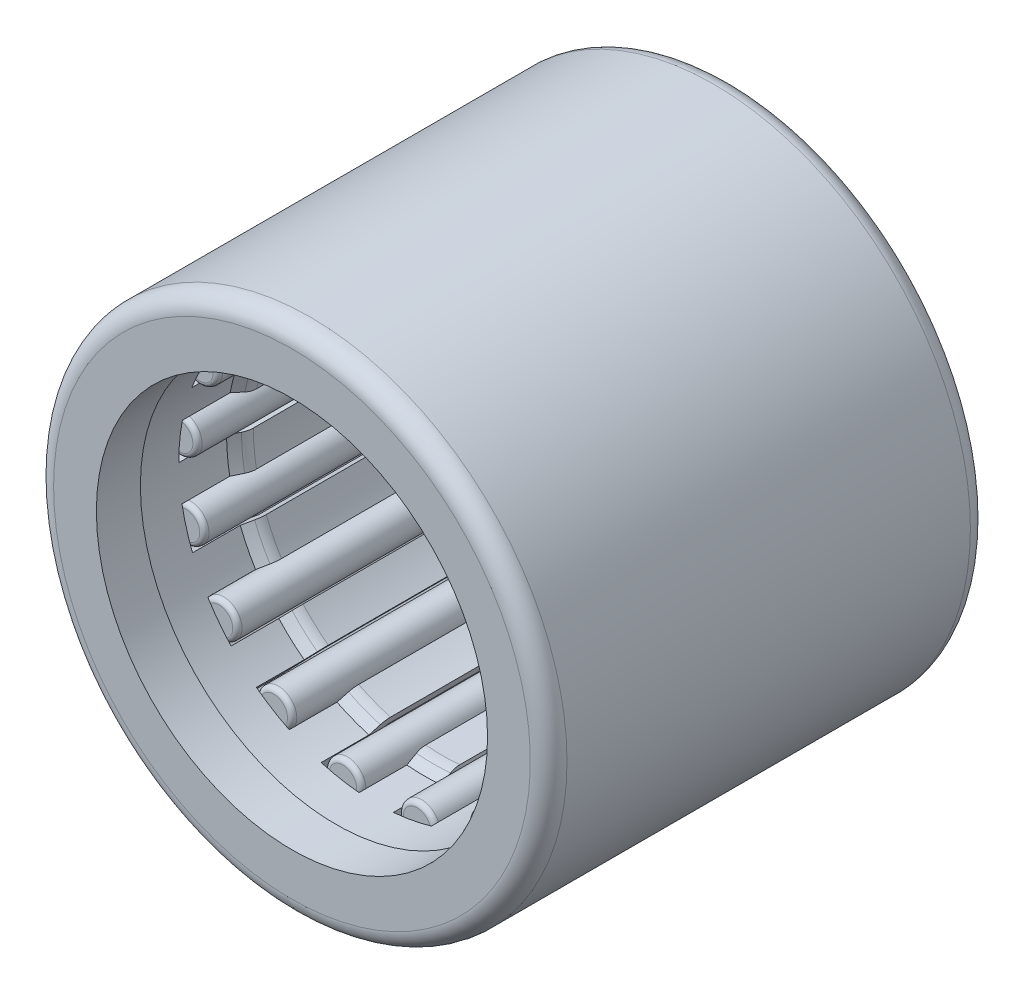
SolidWorks part; units mm, degrees
ref_plane "Front Plane" through (0, 0, 0) normal (0, 0, 1) x (1, 0, 0)
ref_plane "Top Plane" through (0, 0, 0) normal (0, 1, 0) x (1, 0, 0)
ref_plane "Right Plane" through (0, 0, 0) normal (1, 0, 0) x (0, 0, -1)
sketch "Sketch1" plane through (0, 0, 0) normal (0, 0, 1) x (1, 0, 0)
  circle A0 centre (0, 0) radius 5
  circle A1 centre (0, 0) radius 7
  dimension "OD" = 14
  dimension "ID" = 10
sketch "Sketch2" plane through (0, 0, 0) normal (1, 0, 0) x (0, 0, -1)
  line L0 (-6, 0) -> (6, 0) construction
  line L2 (-6, -5) -> (-6, 5) construction
  line L3 (6, 7) -> (-6, 7) construction
  line L11 (0, 0) -> (0, 7) construction
  line L16 (6, -7) -> (6, 7) construction
  line L17 (-6, 5) -> (6, 5) construction
  line L18 (-6, -5) -> (6, -5) construction
  point P4 (0, 0)
  point P8 (0, 7)
  point P10 (-6, 0)
  dimension "For Shaft Diameter" = 10
  dimension "Width" = 12
  dimension "For Housing ID" = 14
sketch "Sketch3" plane through (0, 0, 0) normal (1, 0, 0) x (0, 0, -1)
  line L0 (-6, -5) -> (-6, 5) construction
  line L2 (0, 7) -> (0, 6.3333) construction
  line L3 (0, 6.3333) -> (0, 5.6667) construction
  line L4 (0, 5.6667) -> (0, 5) construction
  line L16 (4.8, 6.3333) -> (4.8, 5.3333)
  line L17 (4.8, 5.3333) -> (6, 5.3333)
  line L18 (6, 5.3333) -> (6, 7)
  line L19 (6, 7) -> (-6, 7)
  line L20 (-6, 7) -> (-6, 5.3333)
  line L21 (-6, 5.3333) -> (-4.8, 5.3333)
  line L22 (-4.8, 5.3333) -> (-4.8, 6.3333)
  line L23 (-4.8, 6.3333) -> (4.8, 6.3333)
  point P17 (0, 5.3333)
  dimension "D1" = 9.6
revolve "Revolve1" add sketch "Sketch3" angle 360 about L0
fillet "Fillet1" radius 0.5 2 edges at (7, 0, -6) (7, 0, 6)
sketch "Sketch4" plane through (0, 0, 0) normal (1, 0, 0) x (0, 0, -1)
  line L0 (0, 6) -> (0, 5.5) construction
  line L2 (-6, 5.3333) -> (-4.8, 5.3333) construction
  line L3 (-3.6, 5) -> (3.6, 5)
  line L4 (-3.6, 5) -> (-3.6, 5.5)
  line L5 (-3.6, 5.5) -> (3.6, 5.5)
  line L6 (3.6, 5) -> (3.6, 5.5)
  line L7 (0, 6.3333) -> (0, 5.6667) construction
  line L8 (-3.6, 5.25) -> (3.6, 5.25) construction
  line L9 (-4.8, 5.3333) -> (-3.6, 5.3333) construction
  point P15 (3.7016, 5.3333)
  point P16 (-3.7016, 5.3333)
  dimension "D1" = 0.1016
revolve "Revolve2" add sketch "Sketch4" angle 360 about L5
fillet "Fillet2" radius 0.127 2 edges at (0.5, 5.5, 3.6) (0.5, 5.5, -3.6)
sketch "Sketch5" plane through (0, 0, 0) normal (0, 0, 1) x (1, 0, 0)
  line L0 (0, 0) -> (0.5, 5.5) construction
  line L1 (0, -5) -> (0, 5) construction
  line L2 (0.5, 5.5) -> (-0.5, 5.5) construction
  line L3 (-0.5, 5.5) -> (0, 0) construction
  circle A0 centre (0, 5.5) radius 0.5
  circle A1 centre (0, 5.5) radius 0.5
  dimension "D1" = 10.389
pattern_circular "CirPattern1" count 17 over 360 about axis through (0, 0, 6) along (0, 0, -1) of bodies 105
sketch "Sketch6" plane through (0, 0, 0) normal (1, 0, 0) x (0, 0, -1)
  line L0 (0, 5.3333) -> (0, 5.6667) construction
  line L1 (-4.8, 5.3841) -> (4.8, 5.3841) construction
  line L2 (-4.8, 5.3841) -> (-4.8, 5.8333)
  line L3 (-4.8, 5.8333) -> (-2.6758, 5.8333) construction
  line L5 (-4.8, 5.3841) -> (-2.4, 5.3841)
  line L6 (-2.4, 5.3841) -> (-2.0233, 5.1667)
  line L7 (-2.0233, 5.1667) -> (2.0233, 5.1667)
  line L8 (4.8, 6.3333) -> (4.8, 5.3333) construction
  line L9 (-4.8, 5.3333) -> (-4.8, 6.3333) construction
  line L10 (-6, 5.3333) -> (-4.8, 5.3333) construction
  line L13 (0, 5) -> (0, 5.3333) construction
  line L14 (0, 5.6667) -> (0, 5) construction
  line L15 (2.4, 5.3841) -> (2.0233, 5.1667)
  line L16 (-4.8, 5.8333) -> (-2.6758, 5.8333)
  line L17 (-2.6758, 5.8333) -> (-1.8978, 5.3841)
  line L18 (-1.8978, 5.3841) -> (1.8978, 5.3841)
  line L21 (-2.0233, 5.1667) -> (-1.8978, 5.3841) construction
  line L22 (4.8, 5.3841) -> (2.4, 5.3841)
  line L23 (4.8, 5.3841) -> (4.8, 5.8333)
  line L24 (4.8, 5.8333) -> (2.6758, 5.8333)
  line L25 (2.6758, 5.8333) -> (1.8978, 5.3841)
  line L26 (0, 5) -> (-1.2, 5) construction
  line L29 (-3.6, 5) -> (3.6, 5) construction
  line L30 (-1.2, 5) -> (-2.4, 5) construction
  line L31 (-2.4, 5) -> (-3.6, 5) construction
  point P10 (0, 5.1667)
  point P18 (0, 5.3333)
  point P24 (0, 5.1667)
  point P28 (0, 5.3841)
  dimension "D1" = 0.0508
  dimension "D2" = 30
revolve "Revolve3" add sketch "Sketch6" angle 360 about L0
fillet "Fillet3" radius 0.508 2 edges at (5.1667, 0, 2.0233) (5.1667, 0, -2.0233)
sketch "Sketch7" plane through (0, 0, 0) normal (0, 0, 1) x (1, 0, 0)
  line L0 (0, 5) -> (0, 5.5) construction
  line L1 (0, 5) -> (0, 5.5) construction
  line L3 (-0.4537, 4.9492) -> (0.4537, 4.9492)
  line L4 (-0.4537, 4.9492) -> (-0.6479, 6.0508)
  line L5 (-0.6479, 6.0508) -> (0.6479, 6.0508)
  line L6 (0.4537, 4.9492) -> (0.6479, 6.0508)
  line L7 (0, 6.0508) -> (0, 4.9492) construction
  line L8 (-0.5508, 5.5) -> (0.5508, 5.5) construction
  circle A0 centre (0, 5.5) radius 0.5 construction
  circle A1 centre (0, 5.5) radius 0.5508 construction
  dimension "D2" = 20
  dimension "D1" = 0.0508
extrude "Cut-Extrude1" cut sketch "Sketch7" along normal up to vertex (3.7016 mm away) and the other way up to vertex (3.7016 mm away) up to point (0, 5.3333, 3.7016) other way up to point (0, 5.3333, -3.7016)
pattern_circular "CirPattern2" count 17 over 360 about axis through (0, 0, 6) along (0, 0, -1) of "Cut-Extrude1"
equation "\"D1@Fillet1\" =  ( \"OD@Sketch1\" - \"For Shaft Diameter@Sketch2\" )  * .125"
equation "\"D1@CirPattern1\" = 360 / \"D1@Sketch5\" / 2"
equation "\"D2\"= \"D1\""
equation "\"D1@CirPattern2\" = \"D1@CirPattern1\""
equation "\"D1@Sketch3\" = \"Width@Sketch2\" * .8"
